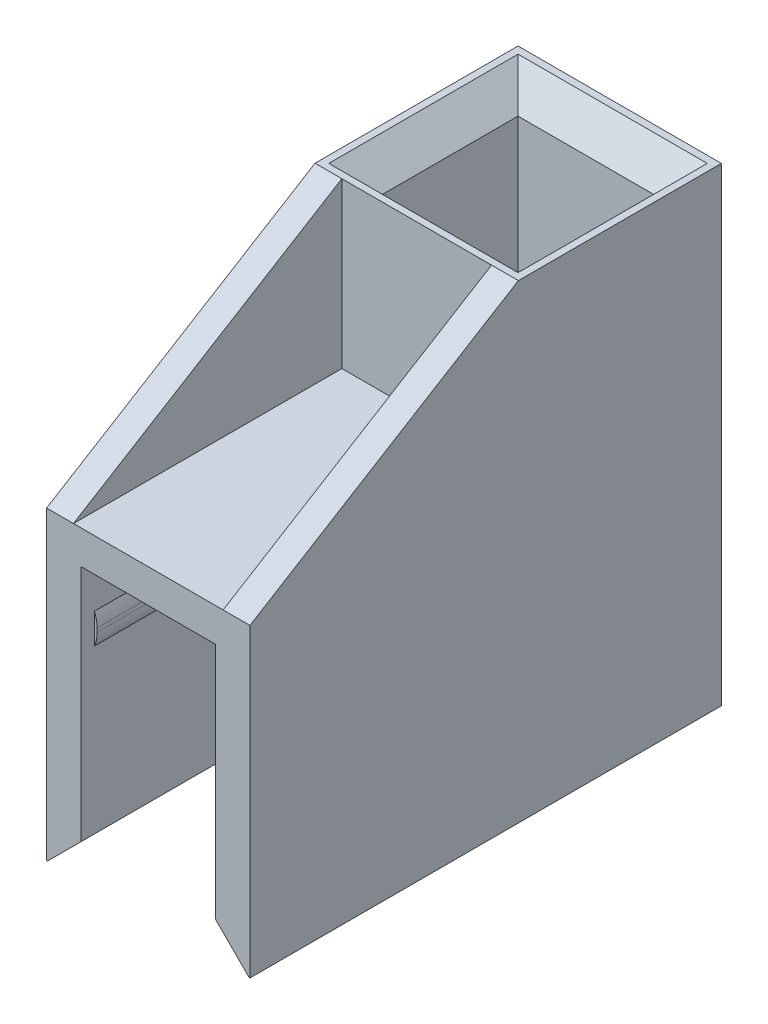
SolidWorks part; units mm, degrees
ref_plane "Alzado" through (0, 0, 0) normal (0, 0, 1) x (1, 0, 0)
ref_plane "Planta" through (0, 0, 0) normal (0, 1, 0) x (1, 0, 0)
ref_plane "Vista lateral" through (0, 0, 0) normal (1, 0, 0) x (0, 0, -1)
sketch "Croquis2" plane through (0, 0, 0) normal (0, 0, 1) x (1, 0, 0)
  line L1 (-15.15, 50) -> (15.15, 50)
  line L2 (-15.15, 50) -> (-15.15, -20)
  line L3 (-15.15, -20) -> (15.15, -20)
  line L4 (15.15, 50) -> (15.15, -20)
  point P0 (0, 50)
  dimension "D1" = 70
  dimension "D2" = 30.3
  dimension "D3" = 20
extrude "Saliente-Extruir2" add sketch "Croquis2" against normal blind 5
sketch "Croquis3" plane through (0, 0, 0) normal (0, 1, 0) x (1, 0, 0)
  line L0 (-15.15, 5) -> (-15.15, 30.25)
  line L1 (-15.15, 30.25) -> (15.15, 30.25)
  line L2 (15.15, 30.25) -> (15.15, 5)
  line L3 (-10.1, 5) -> (-10.1, 25.2)
  line L4 (15.15, 5) -> (-15.15, 5) construction
  line L5 (-10.1, 25.2) -> (10.1, 25.2)
  line L6 (10.1, 25.2) -> (10.1, 5)
  line L7 (0, 25.2) -> (0, 30.25) construction
  line L8 (-10.1, 15.1) -> (-15.15, 15.1) construction
  line L9 (10.1, 15.1) -> (15.15, 15.1) construction
  line L10 (-15.15, 5) -> (15.15, 5)
  line L11 (-10.1, 5) -> (10.1, 5)
  dimension "D1" = 20.2
extrude "Saliente-Extruir3" add sketch "Croquis3" along normal up to surface (50 mm away) from surface contours L0 L10 L3 L5 L6 L2 L1 region at (-14.7556, 0, -17.625) up to face at (0, 50, -2.5) starting at face at (0, -20, -2.5)
sketch "Croquis4" plane through (0, 0, 0) normal (0, 1, 0) x (1, 0, 0)
  line L0 (10.1, 5) -> (-10.1, 5) construction
  line L1 (-10.1, 25.2) -> (10.1, 25.2)
  line L2 (-10.1, 25.2) -> (-10.1, 5)
  line L3 (-10.1, 5) -> (10.1, 5)
  line L4 (10.1, 25.2) -> (10.1, 5)
  line L6 (-10.1, 25.2) -> (-10.1, 5) construction
extrude "Saliente-Extruir4" add sketch "Croquis4" along normal blind 4 from surface starting at face at (0, -20, -15.1)
chamfer "Chaflán4" distance 4 angle 45 4 edges at (0, 50, -5) (10.1, 50, -15.1) (0, 50, -25.2) (-10.1, 50, -15.1)
sketch "Croquis6" plane through (0, 0, 0) normal (0, 0, 1) x (1, 0, 0)
  line L0 (-15.15, 50) -> (-15.15, -20) construction
  line L1 (-15.15, 25.5) -> (15.15, 25.5)
  line L2 (-15.15, 25.5) -> (-15.15, 20.5)
  line L3 (-15.15, 20.5) -> (15.15, 20.5)
  line L4 (15.15, 25.5) -> (15.15, 20.5)
  line L5 (15.15, -20) -> (15.15, 50) construction
  line L6 (-15.15, -20) -> (15.15, -20) construction
  line L8 (-15.15, -20) -> (-10.025, -20)
  line L9 (-15.15, -20) -> (-15.15, 20.5)
  line L10 (-15.15, 20.5) -> (-10.025, 20.5)
  line L11 (-10.025, -20) -> (-10.025, 20.5)
  line L12 (15.15, -20) -> (10.025, -20)
  line L13 (15.15, -20) -> (15.15, 20.5)
  line L14 (15.15, 20.5) -> (10.025, 20.5)
  line L15 (10.025, -20) -> (10.025, 20.5)
  dimension "D1" = 5
  dimension "D2" = 40.5
  dimension "D3" = 20.05
extrude "Saliente-Extruir6" add sketch "Croquis6" along normal blind 40 from surface contours L4 L1 L2 L3 | L8 L11 L3 L9 | L15 L12 L13 L3 region at (0, 23, 0) region at (-12.5875, 0.25, 0) region at (12.5875, 0.25, 0) starting at face at (0, 15, 0)
sketch "Croquis7" plane through (0, 0, 0) normal (1, 0, 0) x (0, 0, -1)
  line L0 (-40, 25.5) -> (0, 50)
  line L1 (0, 50) -> (0, 25.5)
  line L2 (-40, -20) -> (-40, 25.5) construction
  line L3 (0, 25.5) -> (-40, 25.5)
  line L4 (0, 25.5) -> (0, 50) construction
  line L6 (-40, 25.5) -> (0, 25.5) construction
extrude "Saliente-Extruir7" add sketch "Croquis7" along normal up to surface (15.15 mm away) from surface up to face at (15.15, 18.5, 3.25) starting at face at (-15.15, 18.5, 3.25)
sketch "Croquis8" plane through (0, 0, 0) normal (0, 0, 1) x (1, 0, 0)
  line L0 (15.15, 50) -> (-15.15, 50) construction
  line L1 (-11.15, 50) -> (11.15, 50)
  line L2 (-11.15, 50) -> (-11.15, 25.5)
  line L3 (-11.15, 25.5) -> (11.15, 25.5)
  line L4 (11.15, 50) -> (11.15, 25.5)
  line L6 (15.15, 25.5) -> (15.15, 50) construction
  line L7 (15.15, 25.5) -> (-15.15, 25.5) construction
  point P8 (0, 50)
  dimension "D1" = 4
extrude "Cortar-Extruir1" cut sketch "Croquis8" along normal blind 40
chamfer "Chaflán9" distance 5 angle 45 3 edges at (10.025, -20, 20) (-10.025, -20, 20) (0, -20, 0)
sketch "Croquis20" [suppressed] plane through (0, 0, 0) normal (0, 0, 1) x (1, 0, 0)
  line L1 (-15.15, 25.5) -> (15.15, 25.5)
  line L2 (-15.15, 25.5) -> (-15.15, 50)
  line L3 (-15.15, 50) -> (15.15, 50)
  line L4 (15.15, 25.5) -> (15.15, 50)
extrude "Cortar-Extruir2" [suppressed] cut sketch "Croquis20" against normal through all both and the other way through all
sketch "Croquis21" [suppressed] plane through (0, 25.5, 0) normal (0, 1, 0) x (1, 0, 0)
  line L1 (-36.7792, 5) -> (35.3797, 5)
  line L2 (-36.7792, 5) -> (-36.7792, 30.9723)
  line L3 (-36.7792, 30.9723) -> (35.3797, 30.9723)
  line L4 (35.3797, 5) -> (35.3797, 30.9723)
sketch "Croquis22" plane through (-10.025, 0, 0) normal (1, 0, 0) x (0, 0, -1)
  line L0 (0, 20.5) -> (0, -15) construction
  line L1 (-26.8, -6.75) -> (-18.8, -6.75)
  line L2 (-20, 20.5) -> (-20, 13.75) construction
  line L3 (-10, 13.75) -> (-2, 13.75)
  line L5 (-10, 9.25) -> (-2, 9.25)
  line L6 (-2, 13.75) -> (-2, 9.25)
  line L7 (-10, 13.75) -> (-2, 9.25) construction
  line L8 (-10, 9.25) -> (-2, 13.75) construction
  line L9 (-40, 20.5) -> (0, 20.5) construction
  line L10 (-38, 13.75) -> (-38, 9.25)
  line L11 (-30, 9.25) -> (-38, 9.25)
  line L13 (-30, 13.75) -> (-38, 13.75)
  line L14 (-26.8, -6.75) -> (-26.8, -11.25)
  line L15 (-10, -6.75) -> (-2, -6.75)
  line L16 (-10, -6.75) -> (-10, -11.25)
  line L17 (-10, -11.25) -> (-2, -11.25)
  line L18 (-2, -6.75) -> (-2, -11.25)
  line L19 (-10, -6.75) -> (-2, -11.25) construction
  line L20 (-10, -11.25) -> (-2, -6.75) construction
  line L21 (-26.8, -11.25) -> (-18.8, -11.25)
  line L22 (-18.8, -6.75) -> (-18.8, -11.25)
  line L23 (-26.8, -6.75) -> (-18.8, -11.25) construction
  line L24 (-26.8, -11.25) -> (-18.8, -6.75) construction
  line L25 (5, -20) -> (-40, -20) construction
  line L26 (-30, 9.25) -> (-10, 9.25)
  line L27 (-30, 13.75) -> (-10, 13.75)
  line L28 (-20, 9.25) -> (-20, -21.9966) construction
  point P14 (-6, 11.5)
  point P23 (-6, -9)
  dimension "D1" = 2
  dimension "D2" = 4.5
  dimension "D3" = 8
  dimension "D5" = 9
  dimension "D6" = 8
  dimension "D7" = 11
  dimension "D8" = 2
  dimension "D9" = 8.8
  dimension "D10" = 4.5
extrude "Saliente-Extruir9" add sketch "Croquis22" along normal blind 0.4 contours L6 L3 L5 | L13 L10 L11 region at (-10.025, 11.5, 20)
fillet "Redondeo3" radius 5 2 edges at (-9.625, 9.25, 20) (-9.625, 13.75, 20)
sketch "Croquis26" plane through (10.025, 0, 0) normal (-1, 0, 0) x (0, 0, 1)
  line L0 (2, 13.75) -> (10, 13.75)
  line L1 (2, 13.75) -> (2, 9.25)
  line L2 (2, 9.25) -> (10, 9.25)
  line L10 (40, 20.5) -> (0, 20.5) construction
  line L11 (0, 20.5) -> (0, -15) construction
  line L12 (20, 20.5) -> (20, -15) construction
  line L13 (0, -15) -> (40, -15) construction
  line L18 (-5, 2.75) -> (40, 2.75) construction
  line L19 (-5, 25.5) -> (-5, -20) construction
  line L32 (38, 9.25) -> (30, 9.25)
  line L33 (38, 13.75) -> (38, 9.25)
  line L34 (38, 13.75) -> (30, 13.75)
  line L49 (10, 13.75) -> (30, 13.75)
  line L50 (10, 9.25) -> (30, 9.25)
  dimension "D1" = 4.5
  dimension "D2" = 8
  dimension "D4" = 2
extrude "Saliente-Extruir10" add sketch "Croquis26" along normal blind 0.4 contours L33 L34 L32 | L0 L1 L2 region at (10.025, 11.5, 20)
fillet "Redondeo4" radius 5 2 edges at (9.625, 9.25, 20) (9.625, 13.75, 20)
sketch "Croquis27" plane through (0, 25.5, 0) normal (0, 1, 0) x (1, 0, 0)
  line L0 (-42.8964, 5) -> (42.8964, 5)
  line L2 (42.8964, 5) -> (42.8964, 34.3234)
  line L3 (42.8964, 34.3234) -> (-42.8964, 34.3234)
  line L4 (-42.8964, 34.3234) -> (-42.8964, 5)
  point P3 (0, 5)
extrude "Cortar-Extruir3" [suppressed] cut sketch "Croquis27" against normal blind 55
sketch "Croquis28" [suppressed] plane through (0, 25.5, 0) normal (0, 1, 0) x (1, 0, 0)
  line L0 (15.15, -40) -> (15.15, 0) construction
  line L1 (-15.15, 0) -> (15.15, 0)
  line L2 (-15.15, 0) -> (-15.15, -20)
  line L3 (-15.15, -20) -> (15.15, -20)
  line L4 (15.15, 0) -> (15.15, -20)
  dimension "D1" = 20
extrude "Cortar-Extruir4" [suppressed] cut sketch "Croquis28" along normal blind 40
sketch "Croquis29" [suppressed] plane through (0, 25.5, 0) normal (0, 1, 0) x (1, 0, 0)
  line L1 (-15.15, 0) -> (15.15, 0)
  line L2 (-15.15, 0) -> (-15.15, -20)
  line L3 (-15.15, -20) -> (15.15, -20)
  line L4 (15.15, 0) -> (15.15, -20)
extrude "Saliente-Extruir11" [suppressed] add sketch "Croquis29" along normal up to surface (24.5 mm away)
sketch "Croquis30" [suppressed] plane through (0, 50, 0) normal (0, 1, 0) x (1, 0, 0)
  line L0 (11.15, -20) -> (11.15, -40) construction
  line L1 (-11.15, -20) -> (11.15, -20)
  line L2 (-11.15, -20) -> (-11.15, -8.4744)
  line L4 (11.15, -20) -> (11.15, -8.4744)
  line L5 (-11.15, -8.4744) -> (-11.15, -0.05)
  line L7 (11.15, -8.4744) -> (11.15, -0.05)
  line L9 (-11.15, -0.05) -> (11.15, -0.05)
  line L13 (14.1, 1) -> (-14.1, 1) construction
  dimension "D1" = 1.05
extrude "Cortar-Extruir6" [suppressed] cut sketch "Croquis30" against normal up to surface (24.5 mm away)
fillet "Redondeo5" [suppressed] radius 3
fillet "Redondeo7" [suppressed] radius 2
